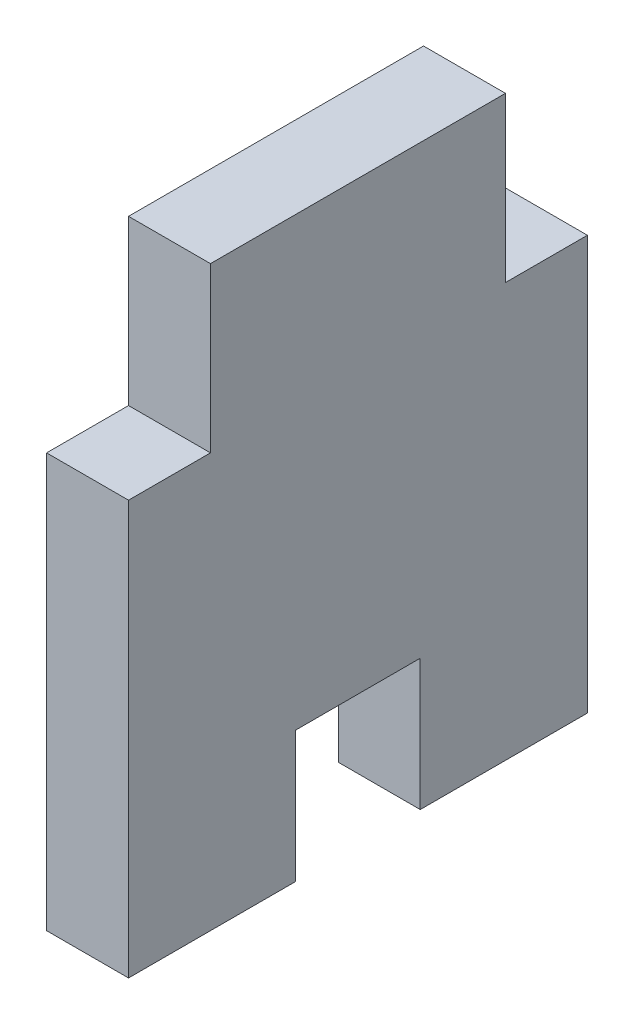
SolidWorks part; units mm, degrees
material "Balsa"
ref_plane "Front Plane" through (0, 0, 0) normal (0, 0, 1) x (1, 0, 0)
ref_plane "Top Plane" through (0, 0, 0) normal (0, 1, 0) x (1, 0, 0)
ref_plane "Right Plane" through (0, 0, 0) normal (1, 0, 0) x (0, 0, -1)
sketch "Sketch1" plane through (0, 0, 0) normal (1, 0, 0) x (0, 0, -1)
  line L0 (0, 0) -> (0, 12.7) construction
  line L1 (11.43, 12.7) -> (-11.43, 12.7)
  line L2 (-11.43, 12.7) -> (-11.43, 0)
  line L3 (-11.43, 0) -> (-17.78, 0)
  line L4 (-17.78, 0) -> (-17.78, -32.0675)
  line L7 (11.43, 12.7) -> (11.43, 0)
  line L8 (11.43, 0) -> (17.78, 0)
  line L9 (17.78, 0) -> (17.78, -32.0675)
  line L13 (-17.78, -32.0675) -> (-4.826, -32.0675)
  line L14 (-4.826, -32.0675) -> (-4.826, -21.9075)
  line L15 (-4.826, -21.9075) -> (4.826, -21.9075)
  line L16 (4.826, -21.9075) -> (4.826, -32.0675)
  line L17 (4.826, -32.0675) -> (17.78, -32.0675)
  point P5 (0, 12.7)
  dimension "D1" = 12.7
  dimension "D2" = 6.35
  dimension "D3" = 6.35
  dimension "D4" = 12.954
  dimension "D5" = 9.652
  dimension "D7" = 10.16
  dimension "Landing Gear Bracket Width" = 22.86
extrude "Boss-Extrude1" add sketch "Sketch1" along normal blind 6.35
